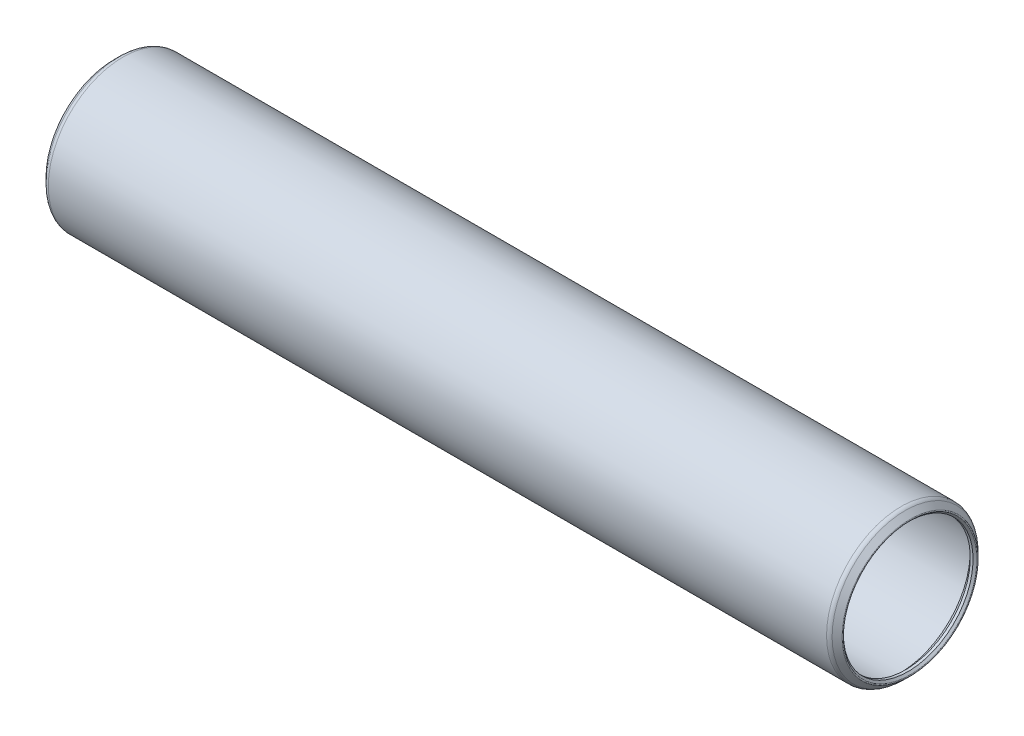
SolidWorks part; units mm, degrees
material "AISI 304"
ref_plane "Front Plane" through (0, 0, 0) normal (0, 0, 1) x (1, 0, 0)
ref_plane "Top Plane" through (0, 0, 0) normal (0, 1, 0) x (1, 0, 0)
ref_plane "Right Plane" through (0, 0, 0) normal (1, 0, 0) x (0, 0, -1)
ref_plane "Plane1" through (108.0897, 0, 0) normal (1, 0, 0) x (0, 0, -1)
sketch "Sketch1" plane through (0, 0, 0) normal (0, 0, 1) x (1, 0, 0)
  line L0 (-0.6395, 9.1676) -> (-0.381, 8.9091)
  line L1 (-0.381, 8.9091) -> (0, 8.9091)
  line L2 (0, 8.9091) -> (0.762, 9.671)
  line L3 (0.762, 9.671) -> (107.3277, 9.671)
  line L4 (107.3277, 9.671) -> (108.0897, 8.9091)
  line L5 (108.0897, 8.9091) -> (108.4707, 8.9091)
  line L6 (108.4707, 8.9091) -> (108.7292, 9.1676)
  line L7 (108.7292, 9.3472) -> (108.0443, 10.0321)
  line L8 (107.5055, 10.2553) -> (0.5842, 10.2553)
  line L9 (0.0454, 10.0321) -> (-0.6395, 9.3472)
  line L10 (108.0897, 0) -> (0, 0) construction
  arc A0 (-0.6395, 9.3472) -> (-0.6395, 9.1676) centre (-0.5497, 9.2574) ccw
  arc A1 (108.7292, 9.1676) -> (108.7292, 9.3472) centre (108.6394, 9.2574) ccw
  arc A2 (108.0443, 10.0321) -> (107.5055, 10.2553) centre (107.5055, 9.4933) ccw
  arc A3 (0.5842, 10.2553) -> (0.0454, 10.0321) centre (0.5842, 9.4933) ccw
revolve "Revolve1" add sketch "Sketch1" angle 360 about L10 reverse direction yes
ref_plane "Plane2" through (54.0448, 0, 0) normal (1, 0, 0) x (0, 0, -1)
ref_plane "cp1 XY" through (54.0448, 0, 0) normal (1, 0, 0) x (0, 0, -1)
ref_plane "cp1 XZ" through (0, 10.2553, 0) normal (0, -1, 0) x (-1, 0, 0)
ref_plane "cp1 YZ" through (0, 0, 0) normal (0, 0, -1) x (-1, 0, 0)
ref_axis "cp1 X" through (54.0448, 10.2553, 80.9) along (0, 0, -1)
ref_axis "cp1 Y" through (54.0448, -50, 0) along (0, 1, 0)
ref_axis "cp1 Z" through (80.9, 10.2553, 0) along (-1, 0, 0)
sketch3d "cp1"
  point P0 (54.0448, 10.2553, 0)
ref_plane "cp2 XY" through (54.0448, 0, 0) normal (1, 0, 0) x (0, 0, -1)
ref_plane "cp2 XZ" through (0, 0, 0) normal (0, -1, 0) x (-1, 0, 0)
ref_plane "cp2 YZ" through (0, 0, -10.2553) normal (0, 0, -1) x (-1, 0, 0)
ref_axis "cp2 X" through (54.0448, 0, 80.9) along (0, 0, -1)
ref_axis "cp2 Y" through (54.0448, -50, -10.2553) along (0, 1, 0)
ref_axis "cp2 Z" through (80.9, 0, -10.2553) along (-1, 0, 0)
sketch3d "cp2"
  point P0 (54.0448, 0, -10.2553)
ref_plane "cp3 XY" through (54.0448, 0, 0) normal (1, 0, 0) x (0, 0, -1)
ref_plane "cp3 XZ" through (0, -10.2553, 0) normal (0, -1, 0) x (-1, 0, 0)
ref_plane "cp3 YZ" through (0, 0, 0) normal (0, 0, -1) x (-1, 0, 0)
ref_axis "cp3 X" through (54.0448, -10.2553, 80.9) along (0, 0, -1)
ref_axis "cp3 Y" through (54.0448, -50, 0) along (0, 1, 0)
ref_axis "cp3 Z" through (80.9, -10.2553, 0) along (-1, 0, 0)
sketch3d "cp3"
  point P0 (54.0448, -10.2553, 0)
ref_plane "cp4 XY" through (54.0448, 0, 0) normal (1, 0, 0) x (0, 0, -1)
ref_plane "cp4 XZ" through (0, 0, 0) normal (0, -1, 0) x (-1, 0, 0)
ref_plane "cp4 YZ" through (0, 0, 10.2553) normal (0, 0, -1) x (-1, 0, 0)
ref_axis "cp4 X" through (54.0448, 0, 80.9) along (0, 0, -1)
ref_axis "cp4 Y" through (54.0448, -50, 10.2553) along (0, 1, 0)
ref_axis "cp4 Z" through (80.9, 0, 10.2553) along (-1, 0, 0)
sketch3d "cp4"
  point P0 (54.0448, 0, 10.2553)
ref_plane "tube_front XY" through (0, 0, 0) normal (1, 0, 0) x (0, 0, -1)
ref_plane "tube_front XZ" through (0, 0, 0) normal (0, -1, 0) x (-1, 0, 0)
ref_plane "tube_front YZ" through (0, 0, 0) normal (0, 0, -1) x (-1, 0, 0)
ref_axis "tube_front X" through (0, 0, 80.9) along (0, 0, -1)
ref_axis "tube_front Y" through (0, -50, 0) along (0, 1, 0)
ref_axis "tube_front Z" through (80.9, 0, 0) along (-1, 0, 0)
sketch3d "tube_front"
  point P0 (0, 0, 0)
ref_plane "tube_rear XY" through (108.0897, 0, 0) normal (1, 0, 0) x (0, 0, -1)
ref_plane "tube_rear XZ" through (0, 0, 0) normal (0, -1, 0) x (-1, 0, 0)
ref_plane "tube_rear YZ" through (0, 0, 0) normal (0, 0, -1) x (-1, 0, 0)
ref_axis "tube_rear X" through (108.0897, 0, 80.9) along (0, 0, -1)
ref_axis "tube_rear Y" through (108.0897, -50, 0) along (0, 1, 0)
ref_axis "tube_rear Z" through (80.9, 0, 0) along (-1, 0, 0)
sketch3d "tube_rear"
  point P0 (108.0897, 0, 0)
